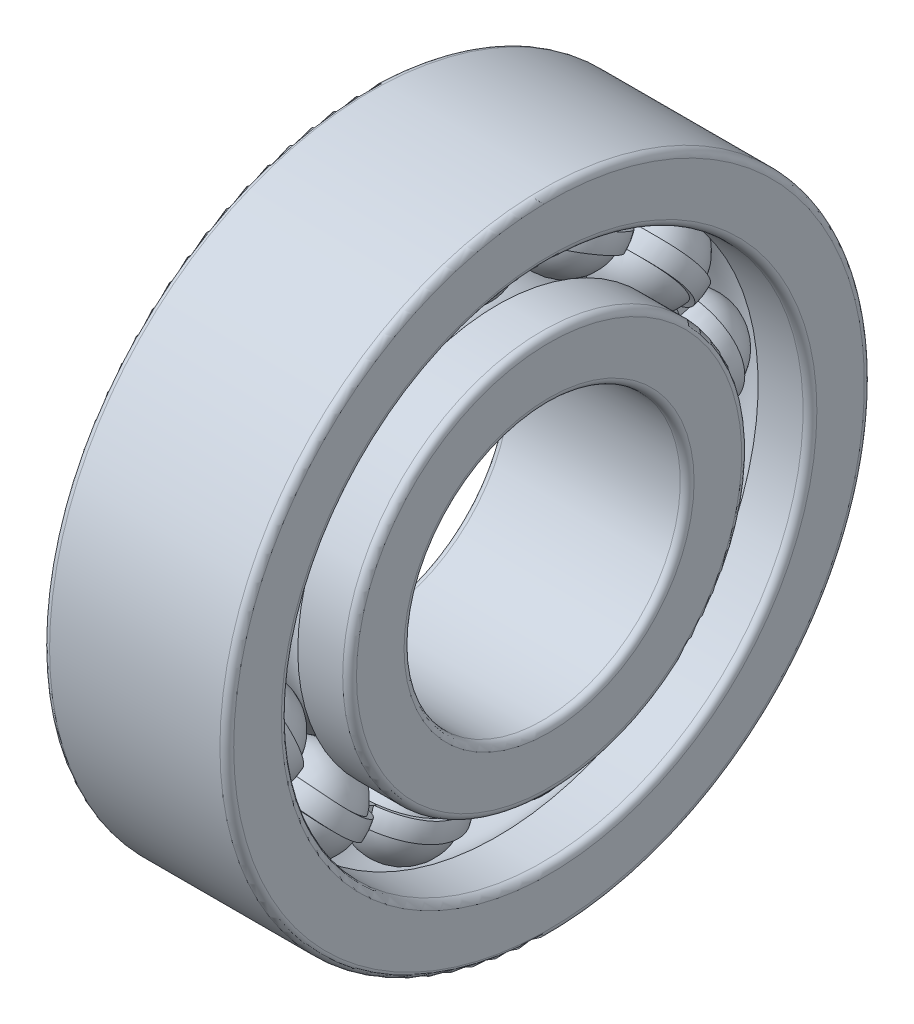
SolidWorks part; units mm, degrees
material "AISI 304"
ref_plane "前视基准面" through (0, 0, 0) normal (0, 0, 1) x (1, 0, 0)
ref_plane "上视基准面" through (0, 0, 0) normal (0, 1, 0) x (1, 0, 0)
ref_plane "右视基准面" through (0, 0, 0) normal (1, 0, 0) x (0, 0, -1)
sketch "尺寸草图" plane through (0, 0, 0) normal (0, 0, 1) x (1, 0, 0)
  line L0 (-19.9271, 0) -> (19.9271, 0) construction
  line L1 (0, 21.603) -> (0, -21.603) construction
  line L2 (-3.7, 14) -> (3.7, 14)
  line L3 (4, 13.7) -> (4, 11.6333)
  line L4 (-4, 13.7) -> (-4, 11.6333)
  line L5 (-3.7, 11.3333) -> (3.7, 11.3333)
  line L6 (-3.5, 10) -> (3.3577, 10) construction
  line L7 (-3.7, 8.6667) -> (3.7, 8.6667)
  line L8 (4, 8.3667) -> (4, 6.3)
  line L9 (3.7, 6) -> (-3.7, 6)
  line L10 (-4, 6.3) -> (-4, 8.3667)
  line L11 (0, 10) -> (0, 12) construction
  circle A0 centre (0, 10) radius 2
  arc A1 (4, 11.6333) -> (3.7, 11.3333) centre (3.7, 11.6333) cw
  arc A2 (4, 8.3667) -> (3.7, 8.6667) centre (3.7, 8.3667) ccw
  arc A3 (-3.7, 8.6667) -> (-4, 8.3667) centre (-3.7, 8.3667) ccw
  arc A4 (-3.7, 11.3333) -> (-4, 11.6333) centre (-3.7, 11.6333) cw
  arc A5 (-3.7, 6) -> (-4, 6.3) centre (-3.7, 6.3) cw
  arc A6 (3.7, 6) -> (4, 6.3) centre (3.7, 6.3) ccw
  arc A7 (4, 13.7) -> (3.7, 14) centre (3.7, 13.7) ccw
  arc A8 (-3.7, 14) -> (-4, 13.7) centre (-3.7, 13.7) ccw
  point P7 (0, 0)
  point P25 (-4, 8.6667)
  point P28 (-4, 11.3333)
  point P31 (-4, 6)
  point P36 (4, 14)
  point P39 (-4, 14)
  dimension "D1" = 0.6667
  dimension "D3" = 0.3
  dimension "B" = 8
  dimension "D2" = 4
  dimension "D" = 28
  dimension "(d)" = 12
  dimension "D5" = 10
  dimension "D6" = 2.6667
  dimension "D7" = 2.6667
sketch "草图2" plane through (0, 0, 0) normal (0, 0, 1) x (1, 0, 0)
  line L6 (3.7, 6) -> (-3.7, 6) construction
  line L8 (-4, 13.7) -> (-4, 11.6333) construction
  line L9 (-3.7, 11.3333) -> (3.7, 11.3333) construction
  line L10 (-3.7, 14) -> (3.7, 14) construction
  line L11 (4, 13.7) -> (4, 11.6333) construction
  line L12 (4, 8.3667) -> (4, 6.3) construction
  line L13 (-3.7, 8.6667) -> (3.7, 8.6667) construction
  line L14 (3.7, 6) -> (-3.7, 6)
  line L15 (-4, 6.3) -> (-4, 8.3667) construction
  line L18 (-3.5, 0) -> (3.5, 0) construction
  line L19 (-19.9271, 0) -> (19.9271, 0) construction
  line L20 (-4, 13.7) -> (-4, 11.6333)
  line L21 (-3.7, 11.3333) -> (-1.4907, 11.3333)
  line L22 (-3.7, 14) -> (3.7, 14)
  line L23 (4, 13.7) -> (4, 11.6333)
  line L24 (4, 8.3667) -> (4, 6.3)
  line L25 (-3.7, 8.6667) -> (-1.4907, 8.6667)
  line L26 (-4, 6.3) -> (-4, 8.3667)
  line L27 (1.4907, 11.3333) -> (3.7, 11.3333)
  line L28 (1.4907, 8.6667) -> (3.7, 8.6667)
  circle A0 centre (0, 10) radius 2 construction
  arc A1 (1.4907, 11.3333) -> (-1.4907, 11.3333) centre (0, 10) ccw
  arc A2 (-1.4907, 8.6667) -> (1.4907, 8.6667) centre (0, 10) ccw
  arc A3 (-3.7, 14) -> (-4, 13.7) centre (-3.7, 13.7) ccw construction
  arc A4 (-4, 11.6333) -> (-3.7, 11.3333) centre (-3.7, 11.6333) ccw construction
  arc A5 (4, 13.7) -> (3.7, 14) centre (3.7, 13.7) ccw construction
  arc A6 (3.7, 11.3333) -> (4, 11.6333) centre (3.7, 11.6333) ccw construction
  arc A7 (4, 8.3667) -> (3.7, 8.6667) centre (3.7, 8.3667) ccw construction
  arc A8 (3.7, 6) -> (4, 6.3) centre (3.7, 6.3) ccw construction
  arc A9 (-3.7, 8.6667) -> (-4, 8.3667) centre (-3.7, 8.3667) ccw construction
  arc A10 (-4, 6.3) -> (-3.7, 6) centre (-3.7, 6.3) ccw construction
  arc A11 (-3.7, 14) -> (-4, 13.7) centre (-3.7, 13.7) ccw
  arc A12 (-4, 11.6333) -> (-3.7, 11.3333) centre (-3.7, 11.6333) ccw
  arc A13 (4, 13.7) -> (3.7, 14) centre (3.7, 13.7) ccw
  arc A14 (3.7, 11.3333) -> (4, 11.6333) centre (3.7, 11.6333) ccw
  arc A15 (4, 8.3667) -> (3.7, 8.6667) centre (3.7, 8.3667) ccw
  arc A16 (3.7, 6) -> (4, 6.3) centre (3.7, 6.3) ccw
  arc A17 (-3.7, 8.6667) -> (-4, 8.3667) centre (-3.7, 8.3667) ccw
  arc A18 (-4, 6.3) -> (-3.7, 6) centre (-3.7, 6.3) ccw
revolve "旋转1" add sketch "草图2" angle 360 about L18
sketch "草图5" plane through (0, 0, 0) normal (0, 0, 1) x (1, 0, 0)
  line L1 (-0.6, 9.6) -> (0.6, 9.6)
  line L2 (-0.6, 9.6) -> (-0.6, 10.4)
  line L3 (-0.6, 10.4) -> (0.6, 10.4)
  line L4 (0.6, 9.6) -> (0.6, 10.4)
  line L5 (-0.6, 9.6) -> (0.6, 10.4) construction
  line L6 (-0.6, 10.4) -> (0.6, 9.6) construction
  circle A0 centre (0, 10) radius 2 construction
  circle A1 centre (0, 10) radius 2 construction
  point P0 (0, 10)
  dimension "D1" = 1.2
  dimension "D2" = 0.8
revolve "旋转3" add sketch "草图5" angle 360 about L0
ref_axis "基准轴1" through (-3.85, 0, 0) along (1, 0, 0)
sketch "草图3" plane through (0, 0, 0) normal (0, 0, 1) x (1, 0, 0)
  line L1 (-2.2, 10) -> (2.2, 10)
  circle A0 centre (0, 10) radius 2 construction
  circle A1 centre (0, 10) radius 2 construction
  arc A2 (2.2, 10) -> (-2.2, 10) centre (0, 10) ccw
  dimension "D2" = 4.4
revolve "旋转2" add sketch "草图3" angle 360 about L1 region at (0, 10.9337, 0)
pattern_circular "阵列(圆周)5" count 13 over 360 about axis through (-3.85, 0, 0) along (1, 0, 0) of bodies 103
sketch "草图6" plane through (0, 0, 0) normal (0, 0, 1) x (1, 0, 0)
  line L0 (-2.1633, 10.4) -> (2.1633, 10.4)
  line L1 (-3.5, 10) -> (4, 10) construction
  line L3 (-2.1633, 9.6) -> (2.1633, 9.6)
  line L4 (4, -13.7) -> (4, 13.7) construction
  arc A0 (-2.1633, 9.6) -> (2.1633, 9.6) centre (0, 10) ccw
  circle A1 centre (0, 10) radius 2 construction
  circle A2 centre (0, 10) radius 2 construction
  arc A3 (2.1633, 10.4) -> (-2.1633, 10.4) centre (0, 10) ccw
  dimension "D1" = 4.4
  dimension "D3" = 0.4
  dimension "D4" = 0.4
revolve "切除-旋转1" cut sketch "草图6" angle 360 about L0
sketch "草图7" plane through (0, 0, 0) normal (0, 0, 1) x (1, 0, 0)
  line L0 (-2, 10) -> (2, 10)
  line L1 (-4, 0) -> (4, 0) construction
  line L2 (-4, 13.7) -> (-4, -13.7) construction
  line L3 (4, -13.7) -> (4, 13.7) construction
  circle A0 centre (0, 10) radius 2 construction
  arc A1 (2, 10) -> (-2, 10) centre (0, 10) ccw
revolve "旋转4" add sketch "草图7" angle 360 about L0
pattern_circular "阵列(圆周)2" count 13 over 360 about axis through (-3.85, 0, 0) along (1, 0, 0) of "旋转4"
